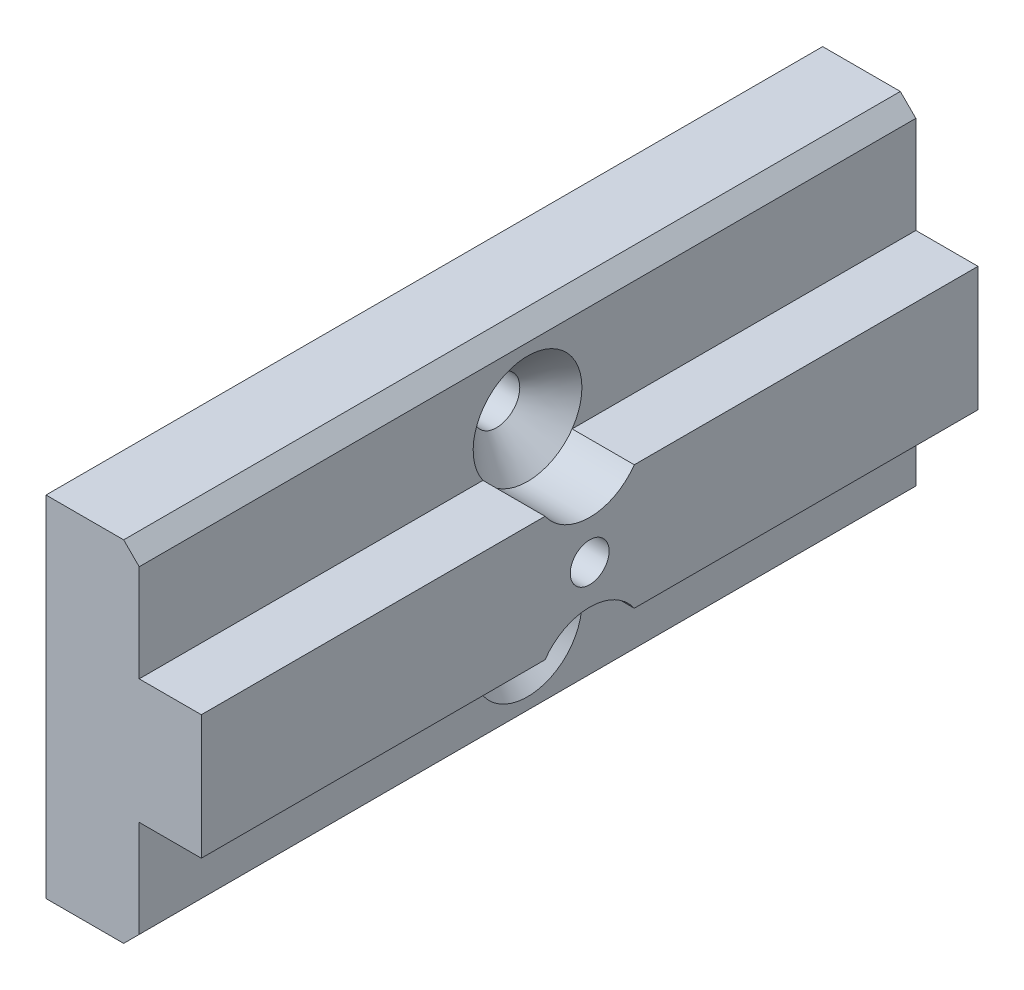
SolidWorks part; units mm, degrees
ref_plane "Front" through (0, 0, 0) normal (0, 0, 1) x (1, 0, 0)
ref_plane "Top" through (0, 0, 0) normal (0, 1, 0) x (1, 0, 0)
ref_plane "Right" through (0, 0, 0) normal (1, 0, 0) x (0, 0, -1)
sketch "草图1" plane through (0, 0, 0) normal (1, 0, 0) x (0, 0, -1)
  line L1 (25, -11.25) -> (-25, -11.25)
  line L2 (25, -11.25) -> (25, 11.25)
  line L3 (25, 11.25) -> (-25, 11.25)
  line L4 (-25, -11.25) -> (-25, 11.25)
  line L5 (25, -11.25) -> (-25, 11.25) construction
  line L6 (25, 11.25) -> (-25, -11.25) construction
  point P0 (0, 0)
  dimension "D1" = 22.5
  dimension "D2" = 50
extrude "凸台-拉伸1" add sketch "草图1" along normal blind 6
sketch "草图2" plane through (6, 0, 0) normal (1, 0, 0) x (0, 0, -1)
  line L0 (-25, 0) -> (25, 0) construction
  line L1 (-25, 11.25) -> (-25, -11.25) construction
  line L2 (25, -11.25) -> (25, 11.25) construction
  line L4 (25, -4) -> (-25, -4)
  line L5 (25, -4) -> (25, 4)
  line L6 (25, 4) -> (-25, 4)
  line L7 (-25, -4) -> (-25, 4)
  line L8 (25, -4) -> (-25, 4) construction
  line L9 (25, 4) -> (-25, -4) construction
  point P6 (0, 0)
  dimension "D1" = 8
extrude "凸台-拉伸2" add sketch "草图2" along normal blind 4
sketch "草图3" plane through (0, 0, 0) normal (-1, 0, 0) x (0, 0, 1)
  line L0 (0, 11.25) -> (0, -11.25) construction
  line L1 (-25, 11.25) -> (25, 11.25) construction
  line L2 (25, -11.25) -> (-25, -11.25) construction
  line L3 (-25, 0) -> (25, 0) construction
  line L4 (-25, -11.25) -> (-25, 11.25) construction
  line L5 (25, 11.25) -> (25, -11.25) construction
  circle A0 centre (0, 6) radius 1.5
  circle A1 centre (0, -6) radius 1.5
  circle A2 centre (0, 0) radius 1.25
  dimension "D1" = 3
  dimension "D2" = 3
  dimension "D4" = 2.5
  dimension "D3" = 12
extrude "切除-拉伸1" cut sketch "草图3" against normal through all
sketch "草图4" plane through (6, 0, 0) normal (1, 0, 0) x (0, 0, -1)
  line L0 (-25.0732, 0) -> (25.1243, 0) construction
  circle A0 centre (0, 6) radius 3.5
  circle A1 centre (0, -6) radius 3.5
  dimension "D1" = 7
  dimension "D2" = 7
extrude "切除-拉伸2" cut sketch "草图4" along normal through all
chamfer "倒角1" distance 2 angle 45 2 edges at (6, -6, -1.5) (6, 6, -1.5)
chamfer "倒角2" distance 1 angle 45 2 edges at (6, -11.25, 0) (6, 11.25, 0)
